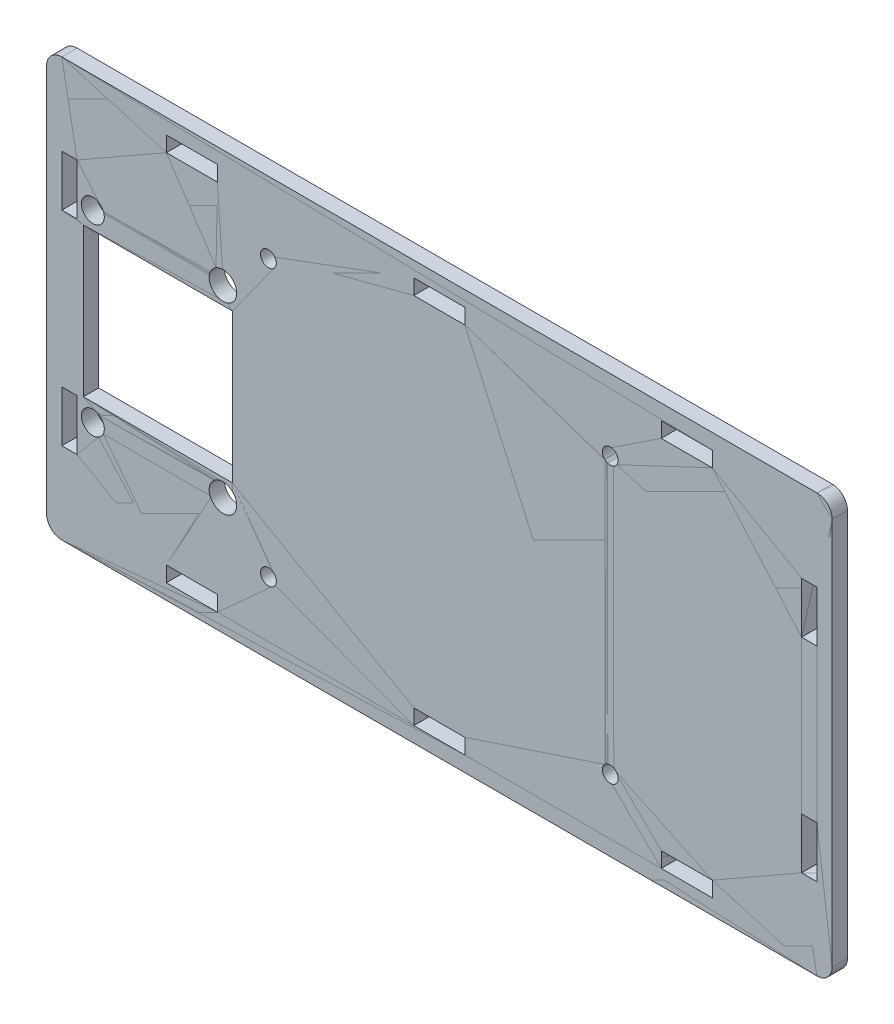
SolidWorks part; units mm, degrees
ref_plane "前视基准面" through (0, 0, 0) normal (0, 0, 1) x (1, 0, 0)
ref_plane "上视基准面" through (0, 0, 0) normal (0, 1, 0) x (1, 0, 0)
ref_plane "右视基准面" through (0, 0, 0) normal (1, 0, 0) x (0, 0, -1)
sketch "草图1" plane through (0, 0, 0) normal (0, 0, 1) x (1, 0, 0)
  line L0 (0, -9.5012) -> (46.4632, -9.5012) construction
  line L1 (-74, 31.4988) -> (74, 31.4988)
  line L2 (-77, 28.4988) -> (-77, -47.5012)
  line L3 (-74, -50.5012) -> (74, -50.5012)
  line L4 (77, 28.4988) -> (77, -47.5012)
  line L5 (-77, 31.4988) -> (77, -50.5012) construction
  line L6 (-77, -50.5012) -> (77, 31.4988) construction
  line L7 (-74, -24.5012) -> (-71, -24.5012)
  line L8 (-74, -24.5012) -> (-74, -34.5012)
  line L9 (-74, -34.5012) -> (-71, -34.5012)
  line L10 (-71, -24.5012) -> (-71, -34.5012)
  line L11 (-74, -24.5012) -> (-71, -34.5012) construction
  line L12 (-74, -34.5012) -> (-71, -24.5012) construction
  line L17 (-53.5, -44.5012) -> (-43.5, -44.5012)
  line L18 (-53.5, -44.5012) -> (-53.5, -47.5012)
  line L19 (-5, -44.5012) -> (5, -44.5012)
  line L20 (-5, -44.5012) -> (-5, -47.5012)
  line L21 (-5, -47.5012) -> (5, -47.5012)
  line L22 (5, -44.5012) -> (5, -47.5012)
  line L23 (-5, -44.5012) -> (5, -47.5012) construction
  line L24 (-5, -47.5012) -> (5, -44.5012) construction
  line L25 (-53.5, -47.5012) -> (-43.5, -47.5012)
  line L26 (-43.5, -44.5012) -> (-43.5, -47.5012)
  line L27 (-53.5, -44.5012) -> (-43.5, -47.5012) construction
  line L28 (-53.5, -47.5012) -> (-43.5, -44.5012) construction
  line L29 (0, -9.5012) -> (0, -75.1961) construction
  line L30 (-5, 28.4988) -> (5, 28.4988)
  line L31 (5, 25.4988) -> (5, 28.4988)
  line L32 (-5, 25.4988) -> (5, 25.4988)
  line L33 (-5, 25.4988) -> (-5, 28.4988)
  line L34 (-53.5, 28.4988) -> (-43.5, 28.4988)
  line L35 (-43.5, 25.4988) -> (-43.5, 28.4988)
  line L36 (-53.5, 25.4988) -> (-43.5, 25.4988)
  line L37 (-53.5, 25.4988) -> (-53.5, 28.4988)
  line L38 (-74, 15.4988) -> (-71, 15.4988)
  line L39 (-71, 5.4988) -> (-71, 15.4988)
  line L40 (-74, 5.4988) -> (-71, 5.4988)
  line L41 (-74, 5.4988) -> (-74, 15.4988)
  line L42 (53.5, -47.5012) -> (43.5, -47.5012)
  line L43 (43.5, -44.5012) -> (43.5, -47.5012)
  line L44 (53.5, -44.5012) -> (43.5, -44.5012)
  line L45 (53.5, -44.5012) -> (53.5, -47.5012)
  line L46 (74, -34.5012) -> (71, -34.5012)
  line L47 (71, -24.5012) -> (71, -34.5012)
  line L48 (74, -24.5012) -> (71, -24.5012)
  line L49 (74, -24.5012) -> (74, -34.5012)
  line L50 (74, 5.4988) -> (74, 15.4988)
  line L51 (74, 5.4988) -> (71, 5.4988)
  line L52 (71, 5.4988) -> (71, 15.4988)
  line L53 (74, 15.4988) -> (71, 15.4988)
  line L54 (53.5, 25.4988) -> (53.5, 28.4988)
  line L55 (53.5, 25.4988) -> (43.5, 25.4988)
  line L56 (43.5, 25.4988) -> (43.5, 28.4988)
  line L57 (53.5, 28.4988) -> (43.5, 28.4988)
  line L59 (-69.7799, 5.0788) -> (-40.5599, 5.0788)
  line L60 (-69.7799, 5.0788) -> (-69.7799, -24.0812)
  line L61 (-69.7799, -24.0812) -> (-40.5599, -24.0812)
  line L62 (-40.5599, 5.0788) -> (-40.5599, -24.0812)
  line L63 (-69.7799, 5.0788) -> (-40.5599, -24.0812) construction
  line L64 (-69.7799, -24.0812) -> (-40.5599, 5.0788) construction
  circle A0 centre (-33.5, 17.5) radius 1.55
  circle A1 centre (-33.5, -36.5025) radius 1.55
  circle A2 centre (33.5, -36.5025) radius 1.55
  circle A3 centre (33.5, 17.5) radius 1.55
  arc A5 (77, -47.5012) -> (74, -50.5012) centre (74, -47.5012) cw
  arc A6 (-74, -50.5012) -> (-77, -47.5012) centre (-74, -47.5012) cw
  arc A7 (74, 31.4988) -> (77, 28.4988) centre (74, 28.4988) cw
  arc A8 (-77, 28.4988) -> (-74, 31.4988) centre (-74, 28.4988) cw
  circle A9 centre (-42.4199, 8.4988) radius 2.7
  circle A10 centre (-67.9199, 8.4988) radius 2.2487
  circle A11 centre (-67.9199, -27.5012) radius 2.2487
  circle A12 centre (-42.4199, -27.5012) radius 2.7
  point P0 (0, -9.5012)
  point P5 (-72.5, -29.5012)
  point P10 (-43.7493, -32.7964)
  point P11 (-45.5, -46.0012)
  point P15 (0, -46.0012)
  point P34 (-48.5, -46.0012)
  point P61 (-55.1699, -9.5012)
  point P80 (0, 0)
  point P87 (0, 0)
  point P88 (0, 0)
  point P89 (0, 0)
  dimension "D9" = 3.1
  dimension "D10" = 3
  dimension "D13" = 3.42
  dimension "D1" = 154
  dimension "D2" = 82
  dimension "D3" = 3
  dimension "D4" = 10
  dimension "D5" = 3
  dimension "D6" = 16
  dimension "D7" = 3
  dimension "D8" = 23.5
  dimension "D11" = 29.22
  dimension "D12" = 29.16
  dimension "D14" = 1.86
  dimension "D15" = 25.5
extrude "凸台-拉伸3" add sketch "草图1<3>" along normal blind 3
sketch "草图1<3>" plane through (0, 0, 0) normal (0, 0, 1) x (1, 0, 0) same geometry as "草图1"
extrude "凸台-拉伸2" add sketch "草图1<2>" along normal blind 3
sketch "草图1<2>" plane through (0, 0, 0) normal (0, 0, 1) x (1, 0, 0) same geometry as "草图1"
extrude "凸台-拉伸1" add sketch "草图1" along normal blind 3
